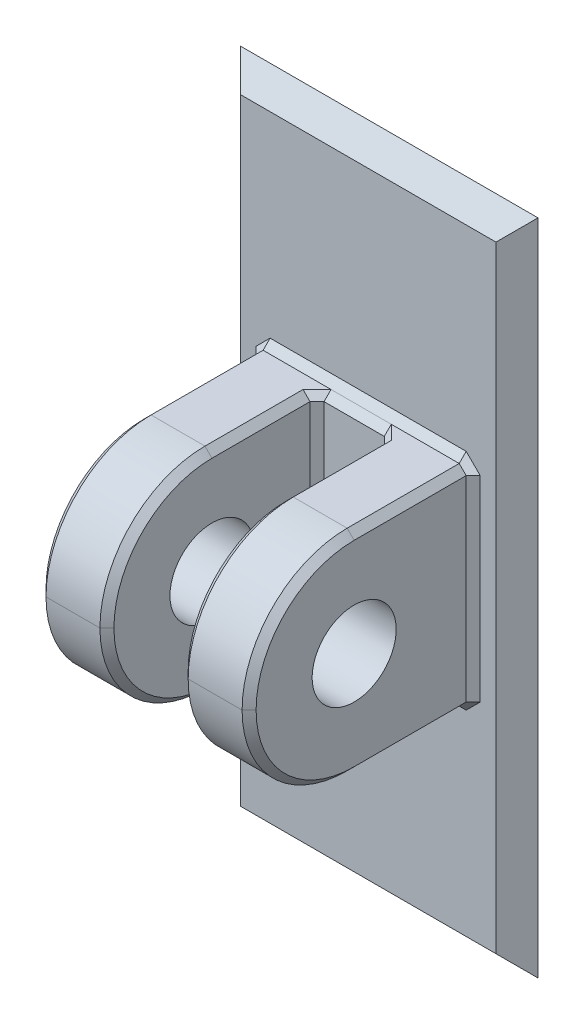
SolidWorks part; units mm, degrees
ref_plane "Front Plane" through (0, 0, 0) normal (0, 0, 1) x (1, 0, 0)
ref_plane "Top Plane" through (0, 0, 0) normal (0, 1, 0) x (1, 0, 0)
ref_plane "Right Plane" through (0, 0, 0) normal (1, 0, 0) x (0, 0, -1)
sketch "Sketch1" plane through (0, 0, 0) normal (0, 0, 1) x (1, 0, 0)
  line L1 (-10.625, 23.5) -> (10.625, 23.5)
  line L2 (-10.625, 23.5) -> (-10.625, -23.5)
  line L3 (-10.625, -23.5) -> (10.625, -23.5)
  line L4 (10.625, 23.5) -> (10.625, -23.5)
  line L5 (-10.625, 23.5) -> (10.625, -23.5) construction
  line L6 (-10.625, -23.5) -> (10.625, 23.5) construction
  point P0 (0, 0)
  dimension "D1" = 21.25
  dimension "D2" = 47
extrude "Boss-Extrude1" add sketch "Sketch1" along normal blind 1.5
chamfer "Chamfer1" distance 1.5 angle 45 4 edges at (0, -23.5, 1.5) (-10.625, 0, 1.5) (0, 23.5, 1.5) (10.625, 0, 1.5)
sketch "Sketch2" plane through (0, 0, 1.5) normal (0, 0, 1) x (1, 0, 0)
  line L1 (-7.5, 7.5) -> (7.5, 7.5)
  line L2 (-7.5, 7.5) -> (-7.5, -7.5)
  line L3 (-7.5, -7.5) -> (7.5, -7.5)
  line L4 (7.5, 7.5) -> (7.5, -7.5)
  line L5 (-7.5, 7.5) -> (7.5, -7.5) construction
  line L6 (-7.5, -7.5) -> (7.5, 7.5) construction
  point P0 (0, 0)
  dimension "D1" = 15
  dimension "D2" = 15
extrude "Boss-Extrude2" add sketch "Sketch2" along normal blind 16
sketch "Sketch3" plane through (0, 0, 17.5) normal (0, 0, 1) x (1, 0, 0)
  line L0 (-7.5, -7.5) -> (7.5, -7.5) construction
  line L1 (-2.65, 7.5) -> (2.65, 7.5)
  line L2 (-2.65, 7.5) -> (-2.65, -7.5)
  line L3 (-2.65, -7.5) -> (2.65, -7.5)
  line L4 (2.65, 7.5) -> (2.65, -7.5)
  line L5 (-2.65, 7.5) -> (2.65, -7.5) construction
  line L6 (-2.65, -7.5) -> (2.65, 7.5) construction
  point P0 (0, 0)
  dimension "D1" = 5.3
extrude "Cut-Extrude1" cut sketch "Sketch3" against normal blind 15
sketch "Sketch4" plane through (-7.5, 0, 0) normal (-1, 0, 0) x (0, 0, 1)
  line L0 (17.5, 7.5) -> (17.5, -7.5) construction
  circle A0 centre (10, 0) radius 3
  dimension "D1" = 6
  dimension "D2" = 7.5
extrude "Cut-Extrude2" cut sketch "Sketch4" against normal through all both and the other way through all
fillet "Fillet1" radius 7.5 4 edges at (5.075, -7.5, 17.5) (5.075, 7.5, 17.5) (-5.075, 7.5, 17.5) (-5.075, -7.5, 17.5)
chamfer "Chamfer2" distance 0.5 angle 45 24 edges at (7.5, -7.5, 5.75) (7.5, -5.3033, 15.3033) (7.5, 5.3033, 15.3033) (7.5, 7.5, 5.75) (2.65, -7.5, 6.25) (2.65, -5.3033, 15.3033) (2.65, 5.3033, 15.3033) (2.65, 7.5, 6.25) (-7.5, -7.5, 5.75) (-7.5, -5.3033, 15.3033) (-7.5, 5.3033, 15.3033) (-7.5, 7.5, 5.75) (-2.65, -7.5, 6.25) (-2.65, -5.3033, 15.3033) (-2.65, 5.3033, 15.3033) (-2.65, 7.5, 6.25) (-2.65, 0, 2.5) (0, -7.5, 2.5) (0, 7.5, 2.5) (2.65, 0, 2.5) (0, -7.5, 1.5) (7.5, 0, 1.5) (-7.5, 0, 1.5) (0, 7.5, 1.5)
